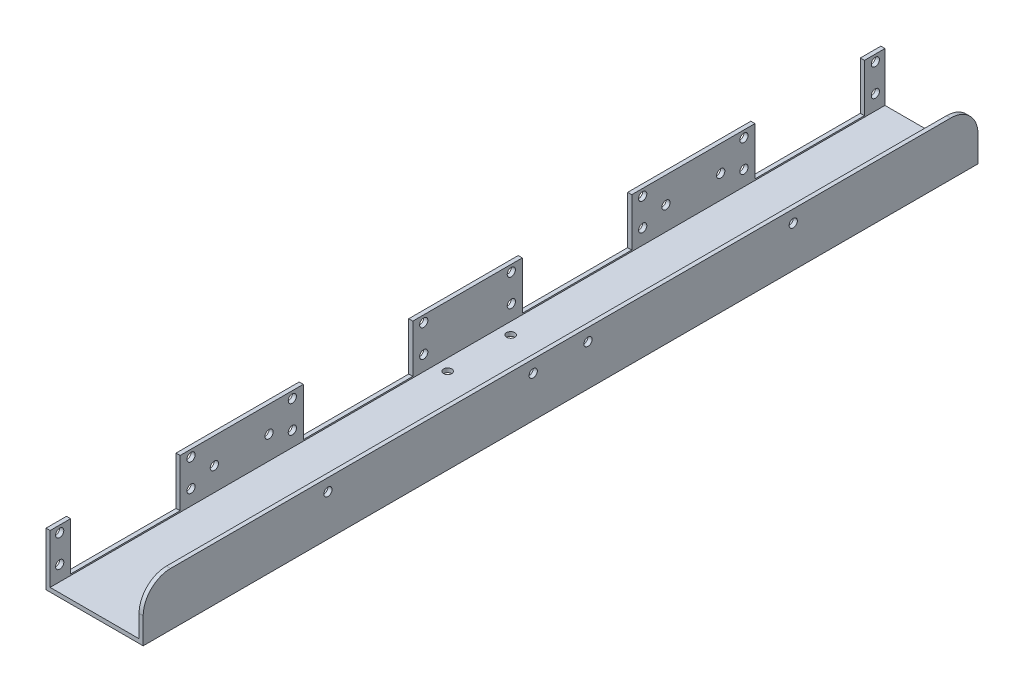
SolidWorks part; units mm, degrees
material "3.0205 (EN-AW 1200)"
ref_plane "Plan de face" through (0, 0, 0) normal (0, 0, 1) x (1, 0, 0)
ref_plane "Plan de dessus" through (0, 0, 0) normal (0, 1, 0) x (1, 0, 0)
ref_plane "Plan de droite" through (0, 0, 0) normal (1, 0, 0) x (0, 0, -1)
sketch "Esquisse1" plane through (0, 0, 0) normal (0, 0, 1) x (1, 0, 0)
  line L0 (-17.75, 19.5) -> (-17.75, 0)
  line L1 (-17.75, 0) -> (17.75, 0)
  line L2 (17.75, 0) -> (17.75, 19.5)
  dimension "D1" = 19.5
  dimension "D2" = 35.5
extrude "Extru.-Mince1" add sketch "Esquisse1" along normal mid plane 305 thin thin type one direction reverse wall 1.5
fillet "Congé1" radius 10 2 edges at (17, 19.5, 152.5) (17, 19.5, -152.5)
sketch "Esquisse2" plane through (0, 0, 0) normal (0, -1, 0) x (1, 0, 0)
  line L0 (0, -10.725) -> (0, 10.725) construction
  line L1 (10.725, 0) -> (-10.725, 0) construction
  circle A0 centre (-12, 11.5) radius 1.5
  circle A1 centre (12, 11.5) radius 1.5
  circle A2 centre (12, -11.5) radius 1.5
  circle A3 centre (-12, -11.5) radius 1.5
  dimension "D1" = 24
  dimension "D2" = 23
  dimension "D3" = 3
extrude "Enlèv. mat.-Extru.1" cut sketch "Esquisse2" against normal blind 2
sketch "Esquisse3" plane through (-17.75, 0, 0) normal (-1, 0, 0) x (0, 0, 1)
  line L0 (152.5, 0) -> (-152.5, 0) construction
  line L1 (-152.5, 19.5) -> (-152.5, 0) construction
  line L2 (-101, 7) -> (-92.5, 10) construction
  line L3 (152.5, 19.5) -> (-152.5, 19.5) construction
  line L4 (-64, 7) -> (-72.5, 10) construction
  line L5 (-149, 17) -> (-145, 17) construction
  line L6 (-145, 19.5) -> (-105, 19.5)
  line L7 (-145, 19.5) -> (-145, 2)
  line L8 (-145, 2) -> (-105, 2)
  line L9 (-105, 19.5) -> (-105, 2)
  line L10 (-60, 19.5) -> (-20, 19.5)
  line L11 (-60, 19.5) -> (-60, 2)
  line L12 (-60, 2) -> (-20, 2)
  line L13 (-20, 19.5) -> (-20, 2)
  line L15 (-105, 17) -> (-101, 17) construction
  line L17 (-64, 17) -> (-60, 17) construction
  circle A0 centre (-149, 17) radius 1.5
  circle A1 centre (-149, 7) radius 1.5
  circle A2 centre (-101, 17) radius 1.5
  circle A3 centre (-101, 7) radius 1.5
  circle A4 centre (-16, 17) radius 1.5
  circle A5 centre (-16, 7) radius 1.5
  circle A6 centre (-64, 17) radius 1.5
  circle A7 centre (-64, 7) radius 1.5
  circle A8 centre (-92.5, 10) radius 1.5
  circle A9 centre (-72.5, 10) radius 1.5
  dimension "D1" = 10
  dimension "D2" = 7
  dimension "D3" = 3
  dimension "D4" = 3.5
  dimension "D7" = 48
  dimension "D8" = 85
  dimension "D9" = 20
  dimension "D10" = 10
  dimension "D11" = 9.5
  dimension "D12" = 2
  dimension "D13" = 40
  dimension "D5" = 2
  dimension "D6" = 2
extrude "Enlèv. mat.-Extru.2" cut sketch "Esquisse3" against normal blind 2
mirror "Symétrie1" about plane through (0, 0, 0) normal (0, 0, 1) of "Enlèv. mat.-Extru.2"
sketch "Esquisse4" plane through (0, 1.5, 0) normal (0, 1, 0) x (1, 0, 0)
  circle A0 centre (12, -24) radius 1.5
  dimension "D1" = 12
  dimension "D3" = 3
  dimension "D2" = 24
extrude "Enlèv. mat.-Extru.3" cut sketch "Esquisse4" against normal blind 2
sketch "Esquisse5" plane through (17.75, 0, 0) normal (1, 0, 0) x (0, 0, -1)
  line L0 (0, 10.725) -> (0, -10.725) construction
  line L1 (-142.5, 19.5) -> (142.5, 19.5) construction
  circle A0 centre (10, 15) radius 1.5
  circle A1 centre (85, 15) radius 1.5
  circle A2 centre (-85, 15) radius 1.5
  circle A3 centre (-10, 15) radius 1.5
  dimension "D1" = 10
  dimension "D2" = 75
  dimension "D3" = 4.5
  dimension "D4" = 3
extrude "Enlèv. mat.-Extru.4" cut sketch "Esquisse5" against normal blind 3
